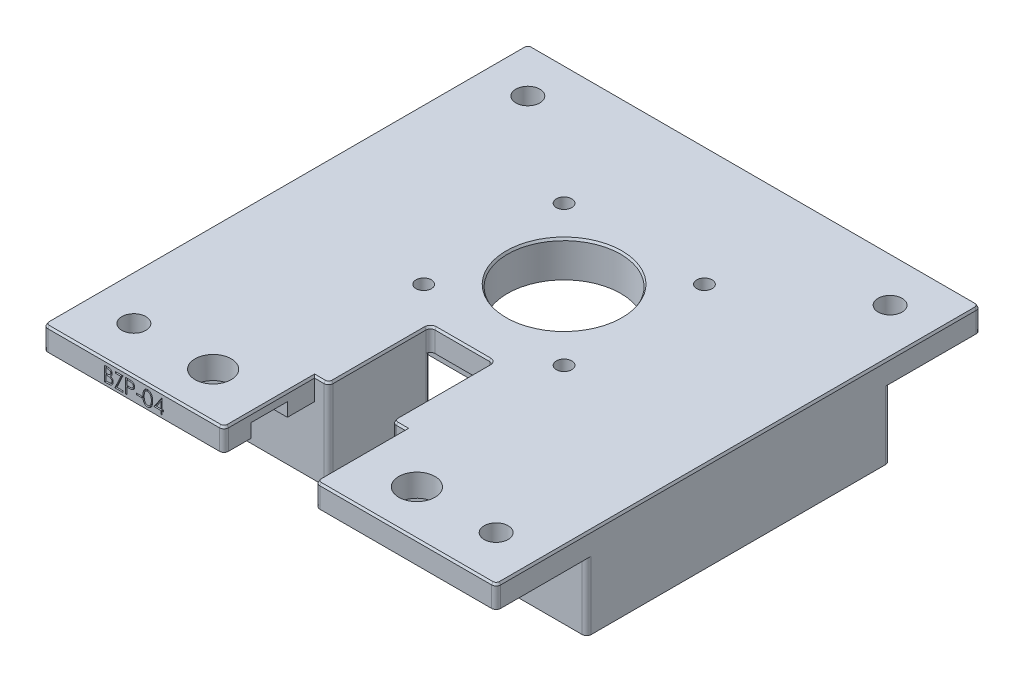
SolidWorks part; units mm, degrees
ref_plane "Front" through (0, 0, 0) normal (0, 0, 1) x (1, 0, 0)
ref_plane "Top" through (0, 0, 0) normal (0, 1, 0) x (1, 0, 0)
ref_plane "Right" through (0, 0, 0) normal (1, 0, 0) x (0, 0, -1)
sketch "Sketch2" plane through (0, 0, 0) normal (0, 1, 0) x (1, 0, 0)
  line L1 (0, 0) -> (100, 0)
  line L2 (0, 0) -> (0, 107)
  line L3 (0, 107) -> (100, 107)
  line L4 (100, 0) -> (100, 107)
  dimension "D1" = 107
  dimension "D2" = 100
extrude "Boss-Extrude1" add sketch "Sketch2" along normal blind 5
sketch "Sketch3" plane through (0, 5, 0) normal (0, 1, 0) x (1, 0, 0)
  line L0 (39.9, 0) -> (39.9, 20)
  line L1 (0, 0) -> (100, 0) construction
  line L2 (39.9, 20) -> (43, 20)
  line L3 (43, 20) -> (43, 42.5)
  line L4 (43, 42.5) -> (57, 42.5)
  line L5 (57, 42.5) -> (57, 20)
  line L6 (57, 20) -> (60.1, 20)
  line L7 (60.1, 20) -> (60.1, 0)
  line L8 (60.1, 0) -> (39.9, 0)
  line L9 (50, 107) -> (50, 65) construction
  line L10 (100, 107) -> (0, 107) construction
  line L11 (43, 42.5) -> (27.5, 42.5) construction
  line L12 (27.5, 87.5) -> (72.5, 87.5) construction
  line L13 (27.5, 87.5) -> (27.5, 42.5) construction
  line L14 (34.5, 49.5) -> (65.5, 49.5) construction
  line L15 (34.5, 49.5) -> (34.5, 80.5) construction
  line L16 (34.5, 80.5) -> (65.5, 80.5) construction
  line L17 (65.5, 49.5) -> (65.5, 80.5) construction
  line L18 (34.5, 49.5) -> (65.5, 80.5) construction
  line L19 (34.5, 80.5) -> (65.5, 49.5) construction
  line L20 (27.5, 42.5) -> (72.5, 42.5) construction
  line L21 (72.5, 87.5) -> (72.5, 42.5) construction
  line L22 (27.5, 87.5) -> (72.5, 42.5) construction
  line L23 (27.5, 42.5) -> (72.5, 87.5) construction
  line L24 (57, 42.5) -> (72.5, 42.5) construction
  line L25 (40, 10) -> (27.5, 10) construction
  line L26 (75, 47) -> (25, 47) construction
  line L27 (75, 47) -> (75, 83) construction
  line L28 (75, 83) -> (25, 83) construction
  line L29 (25, 47) -> (25, 83) construction
  line L30 (75, 47) -> (25, 83) construction
  line L31 (75, 83) -> (25, 47) construction
  line L32 (50, 65) -> (50, 10) construction
  line L33 (40, 0) -> (60, 0) construction
  line L34 (40, 0) -> (40, 20) construction
  line L35 (40, 20) -> (60, 20) construction
  line L36 (60, 0) -> (60, 20) construction
  line L37 (40, 0) -> (60, 20) construction
  line L38 (40, 20) -> (60, 0) construction
  circle A0 centre (50, 65) radius 12.5
  circle A1 centre (65.5, 49.5) radius 1.7
  circle A2 centre (34.5, 49.5) radius 1.7
  circle A3 centre (65.5, 80.5) radius 1.7
  circle A4 centre (34.5, 80.5) radius 1.7
  circle A5 centre (25, 83) radius 1.7 construction
  circle A6 centre (25, 47) radius 1.7 construction
  circle A7 centre (75, 47) radius 1.7 construction
  circle A8 centre (75, 83) radius 1.7 construction
  circle A9 centre (27.5, 10) radius 4
  circle A10 centre (72.5, 10) radius 4
  point P11 (50, 0)
  point P12 (50, 0)
  point P42 (50, 10)
  dimension "D4" = 25
  dimension "D6" = 3.4
  dimension "D10" = 3.4
  dimension "D12" = 8
  dimension "D2" = 14
  dimension "D3" = 20.2
  dimension "D5" = 31
  dimension "D7" = 42
  dimension "D8" = 50
  dimension "D9" = 36
  dimension "D11" = 45
  dimension "D13" = 20
  dimension "D14" = 12.5
  dimension "D15" = 20
extrude "Cut-Extrude1" cut sketch "Sketch3" against normal through all both and the other way through all
hole_wizard "M5 Clearance Hole1" positions "Sketch6" profile "Sketch5" hole size "M5" standard "ANSI Metric" end condition through all
sketch "Sketch6" plane through (0, 5, 0) normal (0, 1, 0) x (1, 0, 0)
  line L0 (0, 97) -> (100, 97) construction
  line L1 (0, 107) -> (0, 0) construction
  line L2 (100, 0) -> (100, 107) construction
  line L5 (10, 107) -> (10, 0) construction
  line L6 (100, 107) -> (0, 107) construction
  line L7 (0, 0) -> (39.9, 0) construction
  line L10 (90, 107) -> (90, 0) construction
  line L11 (60.1, 0) -> (100, 0) construction
  line L14 (0, 10) -> (100, 10) construction
  point P0 (10, 97)
  point P2 (10, 10)
  point P4 (90, 10)
  point P6 (90, 97)
  dimension "D1" = 10
  dimension "D2" = 10
  dimension "D3" = 10
  dimension "D4" = 10
sketch "Sketch5" plane through (10, 5, -97) normal (1, 0, 0) x (0, 0, 1)
  line L0 (0, 0) -> (0, 5)
  line L1 (0, 5) -> (2.65, 5)
  line L2 (2.65, 5) -> (2.65, 0)
  line L5 (2.65, 0) -> (0, 0)
  line L11 (0, -6.35) -> (0, 107.95) construction
  dimension "Thru Hole Dia." = 5.3
  dimension "Thru Hole Depth" = 5
fillet "Fillet1" radius 1 8 edges at (60.1, 2.5, 0) (39.9, 2.5, 0) (0, 2.5, -107) (100, 2.5, -107) (100, 2.5, 0) (0, 2.5, 0) (57, 2.5, -42.5) (43, 2.5, -42.5)
sketch "Sketch7" plane through (0, 0, 0) normal (0, -1, 0) x (1, 0, 0)
  line L0 (57, -20) -> (100, -20)
  line L1 (100, -1) -> (100, -106) construction
  line L2 (100, -20) -> (100, -87)
  line L3 (100, -87) -> (84, -87)
  line L4 (84, -87) -> (84, -82)
  line L5 (84, -82) -> (95, -82)
  line L6 (95, -82) -> (95, -25)
  line L7 (95, -25) -> (57, -25) construction
  line L8 (57, -25) -> (57, -20)
  line L9 (61.1, 0) -> (99, 0) construction
  line L10 (57, -20) -> (57, -41.5) construction
  line L11 (99, -107) -> (1, -107) construction
  line L12 (50, -107) -> (50, -46.1063) construction
  line L13 (43, -25) -> (43, -20)
  line L14 (5, -25) -> (43, -25) construction
  line L15 (5, -82) -> (5, -25)
  line L16 (16, -82) -> (5, -82)
  line L17 (16, -87) -> (16, -82)
  line L18 (0, -87) -> (16, -87)
  line L19 (0, -20) -> (0, -87)
  line L20 (43, -20) -> (0, -20)
  line L21 (57, -25) -> (57, -42.5)
  line L23 (57, -42.5) -> (62, -42.5)
  line L25 (62, -42.5) -> (62, -25)
  line L26 (62, -25) -> (95, -25)
  line L27 (38, -25) -> (5, -25)
  line L28 (38, -42.5) -> (38, -25)
  line L29 (43, -25) -> (43, -42.5)
  line L31 (43, -42.5) -> (38, -42.5)
  line L32 (56, -42.5) -> (44, -42.5) construction
  dimension "D1" = 20
  dimension "D2" = 20
  dimension "D3" = 16
  dimension "D4" = 5
  dimension "D5" = 5
extrude "Boss-Extrude2" add sketch "Sketch7" along normal blind 15
fillet "Fillet3" radius 3 6 edges at (5, -7.5, -82) (95, -7.5, -82) (5, -7.5, -25) (38, -7.5, -25) (95, -7.5, -25) (62, -7.5, -25)
fillet "Fillet4" radius 1 14 edges at (100, -7.5, -87) (100, -7.5, -20) (43, -5, -20) (57, -5, -20) (84, -7.5, -87) (84, -7.5, -82) (0, -7.5, -20) (0, -7.5, -87) (16, -7.5, -87) (16, -7.5, -82) (38, -7.5, -42.5) (62, -7.5, -42.5) (57, -7.5, -42.5) (43, -7.5, -42.5)
ref_plane "Plane1" through (0, 0, -10) normal (0, 0, 1) x (1, 0, 0)
sketch "Sketch9" plane through (0, 0, -10) normal (0, 0, 1) x (1, 0, 0)
  line L0 (39.9, 0) -> (39.9, 3)
  line L2 (39.9, 0) -> (39.9, 5) construction
  line L3 (39.9, 3) -> (36.9, 0)
  line L4 (36.9, 0) -> (39.9, 0)
  line L5 (60.1, 0) -> (63.1, 0)
  line L6 (99, 0) -> (60.1, 0) construction
  line L7 (63.1, 0) -> (60.1, 3)
  line L8 (60.1, 0) -> (60.1, 5) construction
  line L9 (60.1, 3) -> (60.1, 0)
  dimension "D1" = 45
  dimension "D2" = 3
extrude "Cut-Extrude2" cut sketch "Sketch9" against normal blind 4 and the other way blind 4
sketch "Sketch12" plane through (0, 0, 0) normal (0, -1, 0) x (1, 0, 0)
  line L0 (34.5, -85.5) -> (65.5, -85.5)
  line L1 (70.5, -80.5) -> (70.5, -49.5)
  line L2 (65.5, -44.5) -> (34.5, -44.5)
  line L3 (29.5, -49.5) -> (29.5, -80.5)
  circle A0 centre (34.5, -80.5) radius 5 construction
  circle A1 centre (65.5, -80.5) radius 5 construction
  circle A2 centre (65.5, -49.5) radius 5 construction
  circle A3 centre (34.5, -49.5) radius 5 construction
  arc A4 (65.5, -85.5) -> (70.5, -80.5) centre (65.5, -80.5) ccw
  arc A5 (34.5, -85.5) -> (29.5, -80.5) centre (34.5, -80.5) cw
  arc A6 (65.5, -44.5) -> (70.5, -49.5) centre (65.5, -49.5) cw
  arc A7 (29.5, -49.5) -> (34.5, -44.5) centre (34.5, -49.5) cw
  circle A8 centre (50, -65) radius 12.5 construction
  circle A9 centre (50, -65) radius 12.5
  circle A10 centre (34.5, -49.5) radius 1.7 construction
  circle A11 centre (65.5, -49.5) radius 1.7 construction
  circle A12 centre (65.5, -80.5) radius 1.7 construction
  circle A13 centre (34.5, -80.5) radius 1.7 construction
  circle A14 centre (34.5, -49.5) radius 1.7
  circle A15 centre (65.5, -49.5) radius 1.7
  circle A16 centre (65.5, -80.5) radius 1.7
  circle A17 centre (34.5, -80.5) radius 1.7
  dimension "D1" = 10
extrude "Boss-Extrude3" add sketch "Sketch12" along normal blind 3
chamfer "Chamfer2" distance 0.5 angle 45 8 edges at (50, 0, -85.5) (69.0355, 0, -84.0355) (30.9645, 0, -84.0355) (70.5, 0, -65) (29.5, 0, -65) (69.0355, 0, -45.9645) (30.9645, 0, -45.9645) (50, 0, -44.5)
sketch "Sketch10" plane through (0, 5, 0) normal (0, 0, -1) x (1, 0, 0)
  line L0 (0, 4.4) -> (39.9, 4.4) construction
  line L2 (1, 5) -> (38.9, 5) construction
  line L5 (39.9, 0) -> (39.9, 5) construction
  text T0 "BZP-04" font "Century Gothic" height in points 12
  dimension "D1" = 0.6
extrude "Part Num" cut sketch "Sketch10" along normal blind 0.4
chamfer "Printability Chamfer" distance 0.5 angle 30 23 edges at (59.05, 5, -20) (57.2929, 5, -20.2929) (57, 5, -31.25) (56.7071, 5, -42.2071) (50, 5, -42.5) (43.2929, 5, -42.2071) (43, 5, -31.25) (42.7071, 5, -20.2929) (40.95, 5, -20) (50, 5, -77.5) (60.1, 5, -10.5) (60.3929, 5, -0.2929) (80.05, 5, 0) (99.7071, 5, -0.2929) (100, 5, -53.5) (99.7071, 5, -106.7071) (50, 5, -107) (0.2929, 5, -106.7071) (0, 5, -53.5) (39.9, 5, -10.5) (0.2929, 5, -0.2929) (39.6071, 5, -0.2929) (19.95, 5, 0) first distance on face at (72.3667, -3.3333, -20) first distance on face at (57.3964, -5, -20.3964) first distance on face at (57, -4, -33.3) first distance on face at (56.6036, 2.5, -42.1036) first distance on face at (50, 2.5, -42.5) first distance on face at (43.3964, 2.5, -42.1036) first distance on face at (43, -4, -33.3) first distance on face at (42.6036, -5, -20.3964) first distance on face at (27.6333, -3.3333, -20) first distance on face at (50, 5, -77.5) first distance on face at (60.1, 2, -10.25) first distance on face at (60.4964, 2.5, -0.3964) first distance on face at (80.05, 2.5, 0) first distance on face at (99.6036, 2.5, -0.3964) first distance on face at (100, -2.5, -53.5) first distance on face at (99.6036, 2.5, -106.6036) first distance on face at (50, 2.5, -107) first distance on face at (0.3964, 2.5, -106.6036) first distance on face at (0, -2.5, -53.5) first distance on face at (39.9, 2, -10.25) first distance on face at (0.3964, 2.5, -0.3964) first distance on face at (39.5036, 2.5, -0.3964) first distance on face at (16.7139, 2.1875, 0)
equation "\"D5@Sketch7\"=\"D4@Sketch7\""
